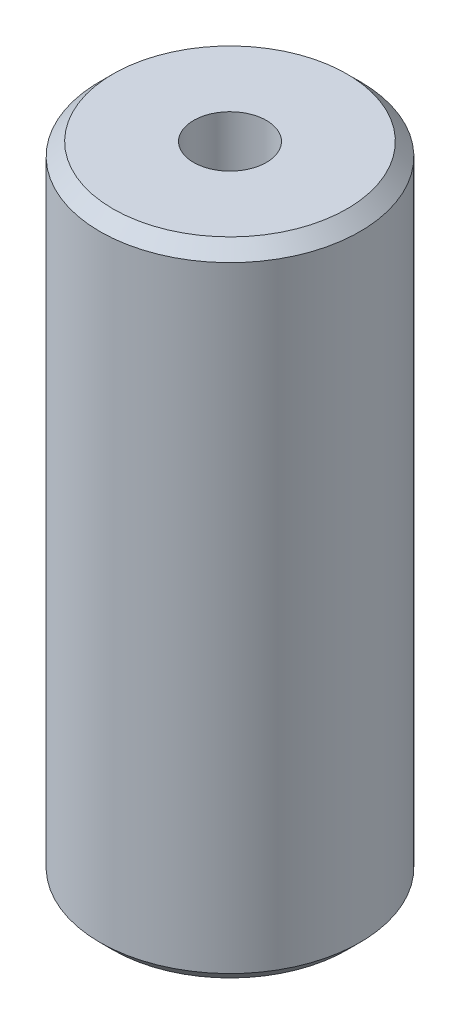
SolidWorks part; units mm, degrees
ref_plane "Front Plane" through (0, 0, 0) normal (0, 0, 1) x (1, 0, 0)
ref_plane "Top Plane" through (0, 0, 0) normal (0, 1, 0) x (1, 0, 0)
ref_plane "Right Plane" through (0, 0, 0) normal (1, 0, 0) x (0, 0, -1)
sketch "Sketch1" plane through (0, 0, 0) normal (0, 1, 0) x (1, 0, 0)
  circle A0 centre (0, 0) radius 17.5
  dimension "SHAFT_OD" = 35
extrude "Boss-Extrude1" add sketch "Sketch1" along normal blind 86.3805
sketch "Sketch2" plane through (0, 0, 0) normal (0, 1, 0) x (1, 0, 0)
  circle A0 centre (0, 0) radius 4.9027
  dimension "BORE_D" = 9.8054
extrude "Cut-Extrude1" cut sketch "Sketch2" along normal through all
chamfer "Chamfer1" distance 1.7598 angle 45 2 edges at (0, 86.3805, 17.5) (0, 0, 17.5)
